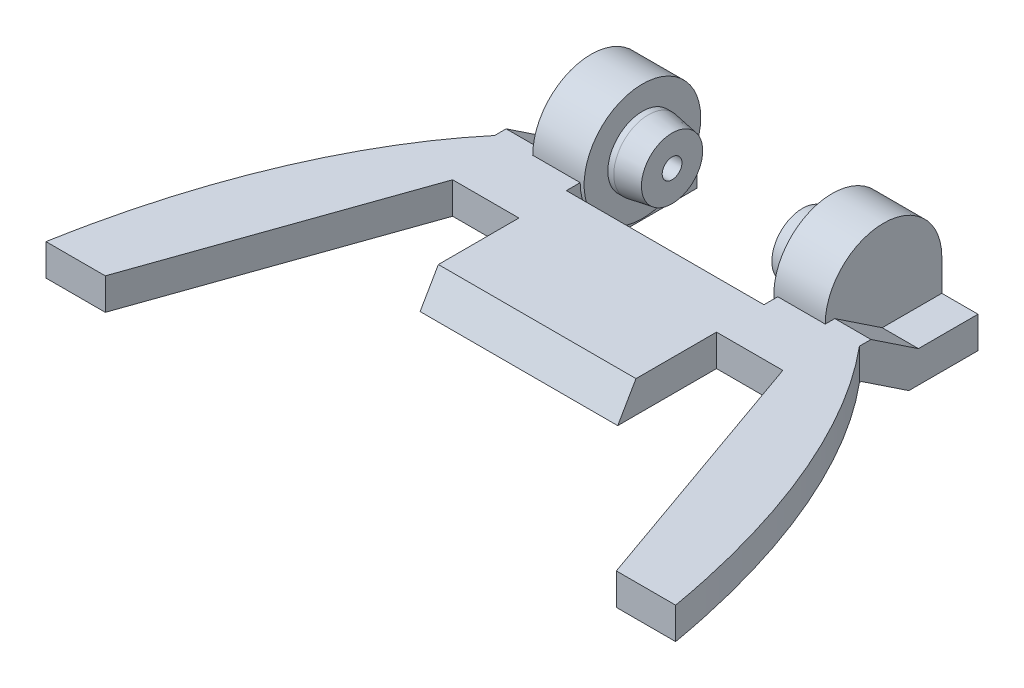
SolidWorks part; units mm, degrees
ref_plane "Front Plane" through (0, 0, 0) normal (0, 0, 1) x (1, 0, 0)
ref_plane "Top Plane" through (0, 0, 0) normal (0, 1, 0) x (1, 0, 0)
ref_plane "Right Plane" through (0, 0, 0) normal (1, 0, 0) x (0, 0, -1)
sketch "Sketch1" plane through (0, 0, 0) normal (0, 1, 0) x (1, 0, 0)
  line L0 (0, 0) -> (0, 58.7756) construction
  line L1 (0, 0) -> (13.1013, 0) construction
  ellipse E0 centre (0, 0) end of major axis (0, 38.1) minor radius 21.209
  dimension "D1" = 42.418
  dimension "D2" = 76.2
extrude "Boss-Extrude1" add sketch "Sketch1" along normal blind 2.032
sketch "Sketch7" plane through (0, 2.032, 0) normal (0, 1, 0) x (1, 0, 0)
  line L0 (-11.7237, 31.75) -> (11.7237, 31.75)
  ellipse E0 centre (0, 0) end of major axis (0, 38.1) minor radius 21.209 construction
  ellipse E1 centre (0, 0) end of major axis (0, 38.1) minor radius 21.209 (11.7237, 31.75) -> (-11.7237, 31.75) ccw
  dimension "D1" = 31.75
extrude "Cut-Extrude6" cut sketch "Sketch7" against normal through all
sketch "Sketch20" plane through (0, 2.032, 0) normal (0, 1, 0) x (1, 0, 0)
  line L1 (-11.7237, 31.75) -> (-6.35, 31.75)
  line L2 (-11.7237, 31.75) -> (-11.7237, 39.37)
  line L3 (-11.7237, 39.37) -> (-6.35, 39.37)
  line L4 (-6.35, 31.75) -> (-6.35, 39.37)
  line L5 (11.7237, 31.75) -> (6.35, 31.75)
  line L6 (11.7237, 31.75) -> (11.7237, 39.37)
  line L7 (11.7237, 39.37) -> (6.35, 39.37)
  line L8 (6.35, 31.75) -> (6.35, 39.37)
  dimension "D1" = 12.7
  dimension "D2" = 7.62
extrude "Boss-Extrude8" add sketch "Sketch20" against normal up to surface (2.032 mm away) up to face at (0, 0, 3.175)
sketch "Sketch21" plane through (0, 0, 0) normal (0, -1, 0) x (1, 0, 0)
  line L0 (-20.2321, -11.43) -> (-16.4221, -11.43)
  line L1 (0, 16.1222) -> (0, 8.0088) construction
  line L2 (-11.7237, -39.37) -> (-6.35, -39.37) construction
  line L3 (-10.6093, -27.94) -> (10.6093, -27.94)
  line L4 (10.6093, -27.94) -> (14.4193, -27.94) construction
  line L5 (-10.6093, -27.94) -> (-14.4193, -27.94) construction
  line L6 (16.4221, -11.43) -> (20.2321, -11.43)
  line L7 (-16.4221, -11.43) -> (-10.6093, -27.94)
  line L8 (16.4221, -11.43) -> (10.6093, -27.94)
  line L9 (-6.35, -31.75) -> (6.35, -31.75) construction
  line L10 (-20.2321, -11.43) -> (-33.5092, -11.43)
  line L11 (-33.5092, -11.43) -> (-33.5092, 55.5739)
  line L12 (-33.5092, 55.5739) -> (36.012, 55.5739)
  line L13 (36.012, 55.5739) -> (36.012, -11.43)
  line L14 (36.012, -11.43) -> (20.2321, -11.43)
  ellipse E0 centre (0, 0) end of major axis (0, -38.1) minor radius 21.209 (11.7237, -31.75) -> (-11.7237, -31.75) ccw construction
  dimension "D1" = 27.94
  dimension "D2" = 3.81
  dimension "D3" = 3.81
extrude "Cut-Extrude12" cut sketch "Sketch21" against normal through all
sketch "Sketch10" plane through (-6.35, 0, 0) normal (1, 0, 0) x (0, 0, -1)
  line L0 (39.37, 2.032) -> (39.37, -2.032)
  line L1 (31.75, 2.032) -> (39.37, 2.032) construction
  line L3 (39.37, -2.032) -> (34.925, -2.032)
  line L4 (34.925, -2.032) -> (31.877, 0)
  line L5 (31.877, 0) -> (31.877, 2.032)
  line L7 (39.37, 0) -> (31.75, 0) construction
  line L8 (31.75, 2.032) -> (39.37, 2.032) construction
  arc A1 (39.37, 2.032) -> (31.877, 2.032) centre (35.6235, 2.032) ccw
  point P6 (35.6235, 2.032)
  dimension "D2" = 3.7465
  dimension "D1" = 2.032
  dimension "D3" = 4.445
  dimension "D4" = 3.048
extrude "Boss-Extrude2" add sketch "Sketch10" against normal blind 3.048
sketch "Sketch11" plane through (-9.398, 0, 0) normal (-1, 0, 0) x (0, 0, 1)
  line L0 (-31.877, 0) -> (-39.37, 0) construction
  line L1 (-31.877, 0) -> (-34.925, -2.032) construction
  line L2 (-34.925, -2.032) -> (-39.37, -2.032) construction
  line L4 (-31.877, 0) -> (-39.37, 0)
  line L5 (-31.877, 0) -> (-34.925, -2.032)
  line L6 (-34.925, -2.032) -> (-39.37, -2.032)
  line L7 (-39.37, -2.032) -> (-39.37, 0)
extrude "Boss-Extrude3" add sketch "Sketch11" along normal up to surface (2.3257 mm away) up to face at (-11.7237, 1.016, -35.56)
sketch "Sketch12" plane through (-9.398, 0, 0) normal (-1, 0, 0) x (0, 0, 1)
  line L2 (-39.37, 0) -> (-44.6386, 0)
  line L3 (-29.7964, 3.8292) -> (-44.6386, 3.8292)
  line L4 (-33.0042, 1.6907) -> (-29.7964, 3.8292)
  line L5 (-39.37, 0) -> (-35.5402, 0)
  line L6 (-35.5402, 0) -> (-33.0042, 1.6907)
  line L7 (-39.37, 0) -> (-35.5402, 0)
  line L8 (-44.6386, 3.8292) -> (-44.6386, 0)
  line L9 (-35.5402, 0) -> (-33.0042, 1.6907)
  dimension "D1" = 2.032
extrude "Cut-Extrude8" cut sketch "Sketch12" along normal through all
sketch "Sketch14" plane through (-6.35, 0, 0) normal (1, 0, 0) x (0, 0, -1)
  circle A0 centre (35.6235, 2.032) radius 3.7465
  arc A2 (39.37, 2.032) -> (31.877, 2.032) centre (35.6235, 2.032) ccw construction
extrude "Boss-Extrude5" add sketch "Sketch14" along normal blind 0.254
sketch "Sketch13" plane through (-6.096, 0, 0) normal (1, 0, 0) x (0, 0, -1)
  circle A0 centre (35.6235, 2.032) radius 2.2225
  dimension "D1" = 4.445
extrude "Boss-Extrude4" add sketch "Sketch13" along normal blind 1.905
chamfer "Chamfer1" distance 1.524 distance2 0.254 1 edges at (-4.191, 2.032, -37.846) first distance on face at (-4.191, 2.032, -37.846)
sketch "Sketch15" plane through (-4.191, 0, 0) normal (1, 0, 0) x (0, 0, -1)
  circle A0 centre (35.6235, 2.032) radius 0.635
  dimension "D1" = 1.27
extrude "Cut-Extrude9" cut sketch "Sketch15" against normal up to surface (2.159 mm away) up to face at (-6.35, -0.2449, -34.417)
sketch "Sketch24" plane through (0, 0, 0) normal (0, 1, 0) x (1, 0, 0)
  line L1 (0, 0) -> (39.238, 0)
  line L2 (0, 0) -> (0, 53.8389)
  line L3 (0, 53.8389) -> (39.238, 53.8389)
  line L4 (39.238, 0) -> (39.238, 53.8389)
extrude "Cut-Extrude14" cut sketch "Sketch24" against normal through all both and the other way through all
sketch "Sketch27" plane through (0, 0, 0) normal (0, -1, 0) x (1, 0, 0)
  line L0 (0, -31.75) -> (0, -27.94) construction
  line L1 (-6.35, -31.75) -> (0, -31.75)
  line L2 (-6.35, -31.75) -> (-6.35, -30.988)
  line L3 (-6.35, -30.988) -> (0, -30.988)
  line L4 (0, -31.75) -> (0, -30.988)
  dimension "D1" = 0.762
extrude "Cut-Extrude16" cut sketch "Sketch27" against normal through all
mirror "Mirror6" about plane through (0, 0, 0) normal (1, 0, 0) of bodies 171 167
sketch "Sketch25" plane through (0, 0, 0) normal (0, -1, 0) x (1, 0, 0)
  line L0 (0, 16.2614) -> (0, 7.9125) construction
  line L1 (-10.6093, -27.94) -> (10.6093, -27.94) construction
  line L2 (-6.35, -27.94) -> (6.35, -27.94)
  line L3 (-6.35, -27.94) -> (-6.35, -21.59)
  line L4 (-6.35, -21.59) -> (6.35, -21.59)
  line L5 (6.35, -27.94) -> (6.35, -21.59)
  dimension "D1" = 12.7
  dimension "D2" = 6.35
extrude "Boss-Extrude10" add sketch "Sketch25" against normal up to surface (2.032 mm away) up to face at (0, 2.032, -27.0655)
sketch "Sketch26" plane through (6.35, 0, 0) normal (1, 0, 0) x (0, 0, -1)
  line L0 (21.59, 0) -> (22.7632, 2.032)
  line L1 (27.94, 2.032) -> (21.59, 2.032) construction
  line L2 (22.7632, 2.032) -> (21.59, 2.032)
  line L3 (21.59, 2.032) -> (21.59, 0)
  dimension "D1" = 60
extrude "Cut-Extrude15" cut sketch "Sketch26" against normal up to surface (12.7 mm away) up to face at (-6.35, 1.016, -24.765)
